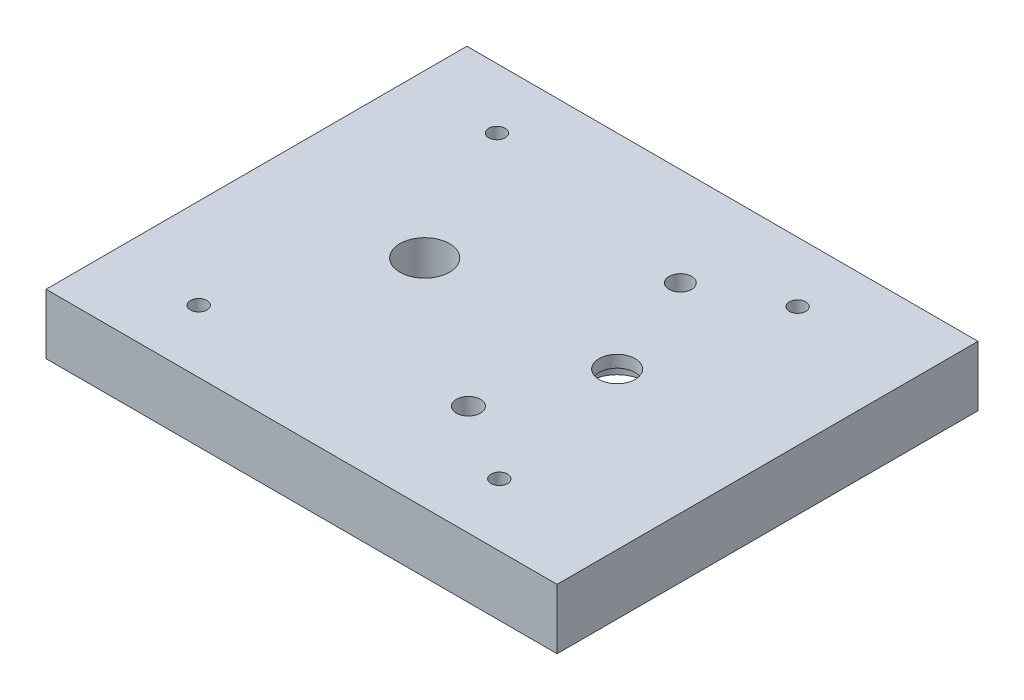
SolidWorks part; units mm, degrees
ref_plane "Front Plane" through (0, 0, 0) normal (0, 0, 1) x (1, 0, 0)
ref_plane "Top Plane" through (0, 0, 0) normal (0, 1, 0) x (1, 0, 0)
ref_plane "Right Plane" through (0, 0, 0) normal (1, 0, 0) x (0, 0, -1)
sketch "Sketch1" plane through (0, 0, 0) normal (0, 1, 0) x (1, 0, 0)
  line L0 (0, 8.2993) -> (0, -7.906) construction
  line L1 (-42.5, 35) -> (42.5, 35)
  line L2 (-42.5, 35) -> (-42.5, -35)
  line L3 (-42.5, -35) -> (42.5, -35)
  line L4 (42.5, 35) -> (42.5, -35)
  line L5 (-42.5, 35) -> (42.5, -35) construction
  line L6 (-42.5, -35) -> (42.5, 35) construction
  line L7 (-12.4915, 0.1967) -> (14.4413, 0.1967) construction
  line L8 (9.5, 1) -> (10.7497, 1) construction
  line L9 (37.5085, 0.1967) -> (64.4413, 0.1967) construction
  line L11 (15.0001, 2.9838) -> (15.0001, -1.0162)
  line L13 (17.9999, 3.0162) -> (17.9999, -0.9838)
  line L14 (15.0001, 2.9838) -> (17.9999, -0.9838) construction
  line L15 (15.0001, -1.0162) -> (17.9999, 3.0162) construction
  line L16 (12.9559, 18.6647) -> (12.9559, 14.773)
  line L17 (5.7059, 18.6647) -> (5.7059, 14.6837)
  line L18 (13.1, -16.7226) -> (13.1, -12.7361)
  line L19 (5.85, -16.7226) -> (5.85, -12.7229)
  line L20 (-7.5, -6) -> (-7.5, 8)
  line L21 (-7.5, -6) -> (-2.8548, -6)
  line L22 (-7.5, 8) -> (-2.8548, 8)
  line L23 (-7.5, -3.7083) -> (-10.5, -3.7083)
  line L24 (-9.7318, -2.1549) -> (-9.7318, 4.1549)
  line L25 (-9.7318, 4.1549) -> (-7.5, 4.1549)
  line L26 (-15.52, 1) -> (-4.4975, 1) construction
  line L28 (-7.5, -4.399) -> (-7.5, 6.399)
  line L29 (-7.5, 6.399) -> (-7.7702, 6.399)
  line L31 (-7.5, -4.399) -> (-9.7318, 6.399) construction
  line L32 (-7.5, 6.399) -> (-9.7318, -4.399) construction
  line L33 (-9.7318, -2.1549) -> (-7.5, -2.1549)
  circle A0 centre (-27.5, 25) radius 1.375
  circle A1 centre (22.5, 25) radius 1.375
  circle A2 centre (22.5, -24.6067) radius 1.375
  circle A3 centre (-27.5, -24.6067) radius 1.375
  circle A4 centre (16.5, 1) radius 10
  circle A5 centre (-15.52, 1) radius 20
  arc A6 (15.0001, 2.9838) -> (17.9999, 3.0162) centre (16.5217, 1.0001) cw
  arc A7 (15.0001, -1.0162) -> (17.9999, -0.9838) centre (16.4783, 0.9999) ccw
  circle A8 centre (16.4783, 0.9999) radius 4.5
  circle A12 centre (-15.52, 1) radius 4.125
  circle A13 centre (16.4783, 0.9999) radius 3
  arc A14 (5.7059, 14.6837) -> (-2.8548, 8) centre (9.5, 1) ccw
  circle A17 centre (85.0307, -10.8481) radius 14
  circle A18 centre (86.1334, -28.3481) radius 2
  circle A19 centre (86.1334, 6.6519) radius 2
  arc A20 (5.7059, 14.6837) -> (-2.8548, 8) centre (9.5, 1) ccw
  circle A21 centre (9.3309, 18.6647) radius 1.875
  circle A22 centre (9.475, -16.7226) radius 2
  arc A23 (12.9559, 18.6647) -> (5.7059, 18.6647) centre (9.3309, 18.6647) ccw
  arc A24 (5.85, -16.7226) -> (13.1, -16.7226) centre (9.475, -16.7226) ccw
  arc A26 (13.1, -12.7361) -> (12.9559, 14.773) centre (9.5, 1) ccw
  arc A27 (13.1, -12.7361) -> (12.9559, 14.773) centre (9.5, 1) ccw
  arc A28 (-2.8548, -6) -> (5.85, -12.7229) centre (9.5, 1) ccw
  arc A29 (-2.8548, -6) -> (5.85, -12.7229) centre (9.5, 1) ccw
  point P0 (0, 0)
  point P61 (-8.6159, 1)
  point P68 (12.9559, 16.7189)
  point P71 (-9.7318, 1)
  dimension "D3" = 15
  dimension "D6" = 2.75
  dimension "D7" = 26
  dimension "D10" = 32.02
  dimension "D11" = 9
  dimension "D12" = 7
  dimension "D13" = 3.75
  dimension "D14" = 17
  dimension "D15" = 1.1027
  dimension "D17" = 1.1027
  dimension "D20" = 8.25
  dimension "D21" = 6
  dimension "D16" = 14
  dimension "D25" = 14.2
  dimension "D1" = 85
  dimension "D2" = 70
  dimension "D4" = 10
  dimension "D8" = 4
  dimension "D9" = 3
  dimension "D18" = 36
  dimension "D19" = 4
  dimension "D22" = 28.9915
  dimension "D23" = 7
  dimension "D24" = 3.9049
  dimension "D26" = 3.9049
  dimension "D27" = 3.9049
  dimension "D28" = 2.2917
  dimension "D29" = 0
  dimension "D30" = 10.798
  dimension "D31" = 7.25
  dimension "D32" = 7.25
  dimension "D33" = 4.6452
  dimension "D5" = 2
extrude "Boss-Extrude4" add sketch "Sketch1" along normal blind 10 contours L4 L1 L2 L3 A14 A4 A5 A2 A1 A0 A3 | A14 A5 | A14 A4 | A5 A14 A4 | A5 A14 | A4 A14 A8 | A8 A13 | A4 A14 A5 | L16 A23 L17 A14 A20 A21 | L19 A24 L18 A14 A22 region at (0, 0, -33.8989) region at (12.4878, 0, -16.7189) region at (23.4362, 0, -1) region at (24.131, 0, -1) region at (-1.5802, 0, -10.7229) region at (-1.3885, 0, -1) region at (12.1056, 0, -0.9999)
sketch "Sketch2" plane through (0, 10, 0) normal (0, 1, 0) x (1, 0, 0)
  circle A3 centre (-15.52, 1) radius 9.125
  circle A4 centre (-15.52, 1) radius 9.125
  dimension "D1" = 5
extrude "Cut-Extrude2" cut sketch "Sketch1<7>" along normal blind 6 contours A8
sketch "Sketch1<7>" plane through (0, 0, 0) normal (0, 1, 0) x (1, 0, 0) same geometry as "Sketch1"
extrude "Cut-Extrude6" cut sketch "Sketch1<9>" along normal blind 6 contours L18 A26 A4 L16 A23 L17 A14 A5 L19 A24 A21 A22 | A5 A14 | A4 A26 A8 | L24 L33 L28 L25 region at (12.4878, 0, -16.7189) region at (23.4362, 0, -1) region at (-1.3885, 0, -1) region at (-8.6159, 0, -1)
sketch "Sketch1<9>" plane through (0, 0, 0) normal (0, 1, 0) x (1, 0, 0) same geometry as "Sketch1"
extrude "Cut-Extrude10" cut sketch "Sketch1<11>" along normal blind 8 contours A8 A13 region at (12.1056, 0, -0.9999)
sketch "Sketch1<11>" plane through (0, 0, 0) normal (0, 1, 0) x (1, 0, 0) same geometry as "Sketch1"
sketch "Sketch5" plane through (0, 10, 0) normal (0, 1, 0) x (1, 0, 0)
  line L1 (-9.7318, -2.1549) -> (-7.5, -2.1549)
  line L2 (-9.7318, -2.1549) -> (-9.7318, 4.1549)
  line L3 (-9.7318, 4.1549) -> (-7.5, 4.1549)
  line L4 (-7.5, -2.1549) -> (-7.5, 4.1549)
extrude "Boss-Extrude5" add sketch "Sketch5" against normal blind 4
